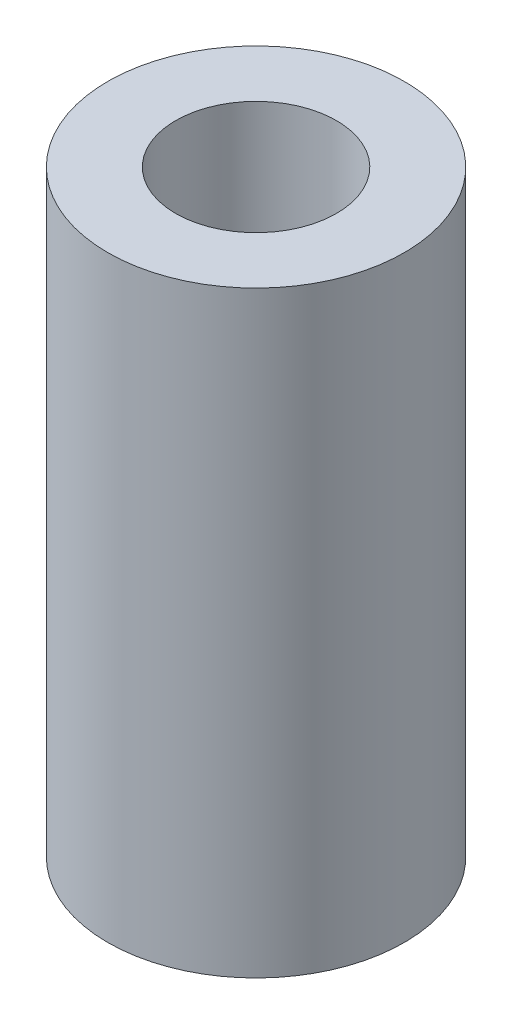
SolidWorks part; units mm, degrees
ref_plane "Front Plane" through (0, 0, 0) normal (0, 0, 1) x (1, 0, 0)
ref_plane "Top Plane" through (0, 0, 0) normal (0, 1, 0) x (1, 0, 0)
ref_plane "Right Plane" through (0, 0, 0) normal (1, 0, 0) x (0, 0, -1)
sketch "Sketch1" plane through (0, 0, 0) normal (0, 1, 0) x (1, 0, 0)
  circle A0 centre (0, 0) radius 10
  dimension "SLEEVE_OD" = 20
extrude "Boss-Extrude1" add sketch "Sketch1" along normal blind 40.29
sketch "Sketch2" plane through (0, 0, 0) normal (0, 1, 0) x (1, 0, 0)
  circle A0 centre (0, 0) radius 5.4249
  dimension "BORE_D" = 10.8498
extrude "Cut-Extrude1" cut sketch "Sketch2" along normal through all
chamfer "Chamfer1" distance 1.7899 angle 65.653 rebuild error yes
